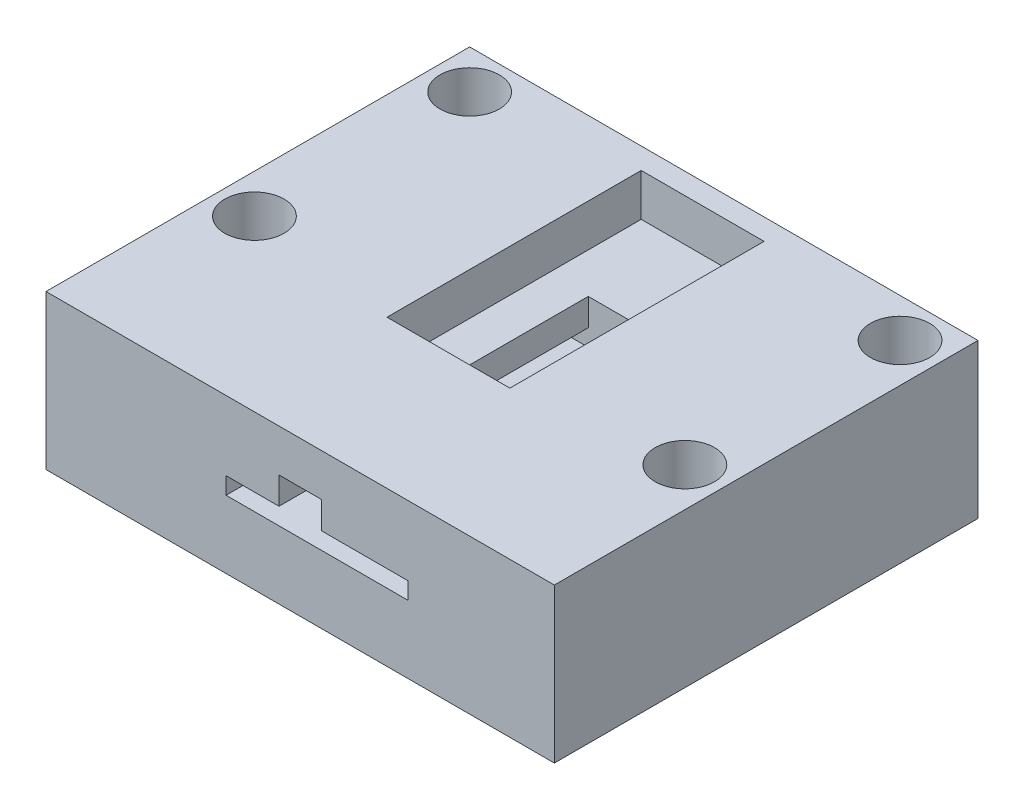
SolidWorks part; units mm, degrees
ref_plane "Front Plane" through (0, 0, 0) normal (0, 0, 1) x (1, 0, 0)
ref_plane "Top Plane" through (0, 0, 0) normal (0, 1, 0) x (1, 0, 0)
ref_plane "Right Plane" through (0, 0, 0) normal (1, 0, 0) x (0, 0, -1)
sketch "Sketch2" plane through (0, 0, 0) normal (0, 1, 0) x (1, 0, 0)
  line L1 (0, 0) -> (60, 0)
  line L2 (0, 0) -> (0, 50)
  line L3 (0, 50) -> (60, 50)
  line L4 (60, 0) -> (60, 50)
  dimension "D1" = 50
  dimension "D2" = 60
extrude "Boss-Extrude1" add sketch "Sketch2" along normal blind 10
sketch "Sketch3" plane through (0, 10, 0) normal (0, 1, 0) x (1, 0, 0)
  line L0 (60, 50) -> (0, 50) construction
  line L1 (21.25, 36.5) -> (42.75, 36.5)
  line L2 (21.25, 36.5) -> (21.25, 0)
  line L3 (21.25, 0) -> (42.75, 0)
  line L4 (42.75, 36.5) -> (42.75, 0)
  line L5 (0, 0) -> (60, 0) construction
  circle A0 centre (30, 32.5) radius 2.25 construction
  point P9 (30, 50)
  dimension "D4" = 4.5
  dimension "D1" = 21.5
  dimension "D3" = 4
  dimension "D5" = 8.75
  dimension "D6" = 17.5
extrude "Cut-Extrude2" cut sketch "Sketch3" against normal blind 2
sketch "Sketch4" plane through (0, 10, 0) normal (0, 1, 0) x (1, 0, 0)
  line L0 (27.5, 50) -> (27.5, 0)
  line L1 (0, 50) -> (60, 50)
  line L2 (0, 50) -> (0, 0)
  line L3 (0, 0) -> (60, 0)
  line L4 (60, 50) -> (60, 0)
  line L5 (32.5, 50) -> (32.5, 0)
  line L6 (27.5, 32.5) -> (32.5, 32.5)
  point P14 (30, 32.5)
  line M12 (0, 0) -> (21.25, 0)
  line M13 (21.25, 0) -> (21.25, 36.5)
  line M14 (21.25, 36.5) -> (42.75, 36.5)
  line M15 (42.75, 36.5) -> (42.75, 0)
  line M16 (42.75, 0) -> (60, 0)
  line M17 (60, 0) -> (60, 50)
  line M18 (60, 50) -> (0, 50)
  line M19 (0, 50) -> (0, 0)
  dimension "D1" = 5
extrude "Boss-Extrude2" add sketch "Sketch4" along normal blind 3.2 contours L5 M18 M14 M15 M16 M17 | L5 L3 M14 M15 | L3 L0 M13 M14 | L0 M18 M19 M12 M13 M14 | L5 L1 L0 M14 region at (24.375, 10, -18.25) region at (11.6366, 10, -26.3426) region at (30, 10, -43.25) region at (37.625, 10, -18.25) region at (49.474, 10, -27.5231)
sketch "Sketch5" plane through (0, 13.2, 0) normal (0, 1, 0) x (1, 0, 0)
  line L1 (0, 50) -> (60, 50)
  line L2 (0, 50) -> (0, 0)
  line L3 (0, 0) -> (60, 0)
  line L4 (60, 50) -> (60, 0)
  line L5 (22.75, 47.5) -> (37.25, 47.5)
  line L6 (22.75, 47.5) -> (22.75, 17.5)
  line L7 (22.75, 17.5) -> (37.25, 17.5)
  line L8 (37.25, 47.5) -> (37.25, 17.5)
  point P4 (30, 47.5)
  point P5 (37.25, 32.5)
  dimension "D1" = 30
  dimension "D2" = 14.5
extrude "Boss-Extrude3" add sketch "Sketch5" along normal blind 5
sketch "Sketch1" plane through (0, 13.2, 0) normal (0, 1, 0) x (1, 0, 0)
  line L5 (4.6, 45.4) -> (55.4, 45.4) construction
  line L6 (4.6, 45.4) -> (4.6, 20) construction
  line L7 (4.6, 20) -> (55.4, 20) construction
  line L8 (55.4, 45.4) -> (55.4, 20) construction
  line L9 (60, 50) -> (0, 50) construction
  line L10 (4.6, 45.4) -> (0, 45.4)
  line L12 (4.6, 45.4) -> (4.6, 50)
  line L13 (0, 50) -> (0, 0) construction
  circle A0 centre (4.6, 20) radius 3.5
  circle A1 centre (4.6, 45.4) radius 3.5
  circle A2 centre (55.4, 45.4) radius 3.5
  circle A3 centre (55.4, 20) radius 3.5
  point P0 (30, 50)
  point P1 (30, 45.4)
  dimension "D3" = 7
  dimension "D1" = 25.4
  dimension "D2" = 50.8
extrude "Cut-Extrude1" cut sketch "Sketch1" against normal through all both and the other way through all contours L12 A1 L10 | L10 A1 L12 | A2 | A0 | A3 region at (5.0951, 13.2, -44.9049) region at (3.1146, 13.2, -46.8854) region at (4.6, 13.2, -20) region at (55.4, 13.2, -45.4) region at (55.4, 13.2, -20)
